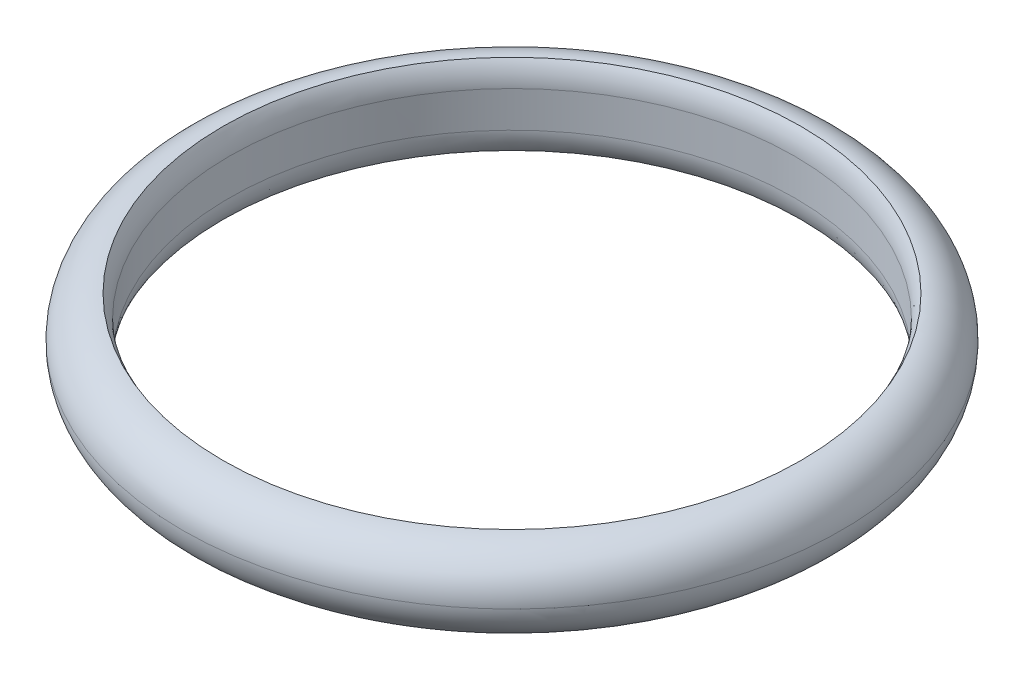
SolidWorks part; units mm, degrees
ref_plane "Front Plane" through (0, 0, 0) normal (0, 0, 1) x (1, 0, 0)
ref_plane "Top Plane" through (0, 0, 0) normal (0, 1, 0) x (1, 0, 0)
ref_plane "Right Plane" through (0, 0, 0) normal (1, 0, 0) x (0, 0, -1)
sketch "Sketch1" plane through (0, 0, 0) normal (0, 1, 0) x (1, 0, 0)
  circle A0 centre (0, 0) radius 12.25
  circle A1 centre (0, 0) radius 10.5
  dimension "D1" = 24.5
  dimension "D2" = 21
extrude "Boss-Extrude1" add sketch "Sketch1" along normal blind 3
fillet "Fillet1" radius 1.5 2 edges at (0, 0, 12.25) (0, 3, 12.25)
fillet "Fillet2" radius 1.5 2 edges at (0, 0, 10.5) (0, 3, 10.5)
